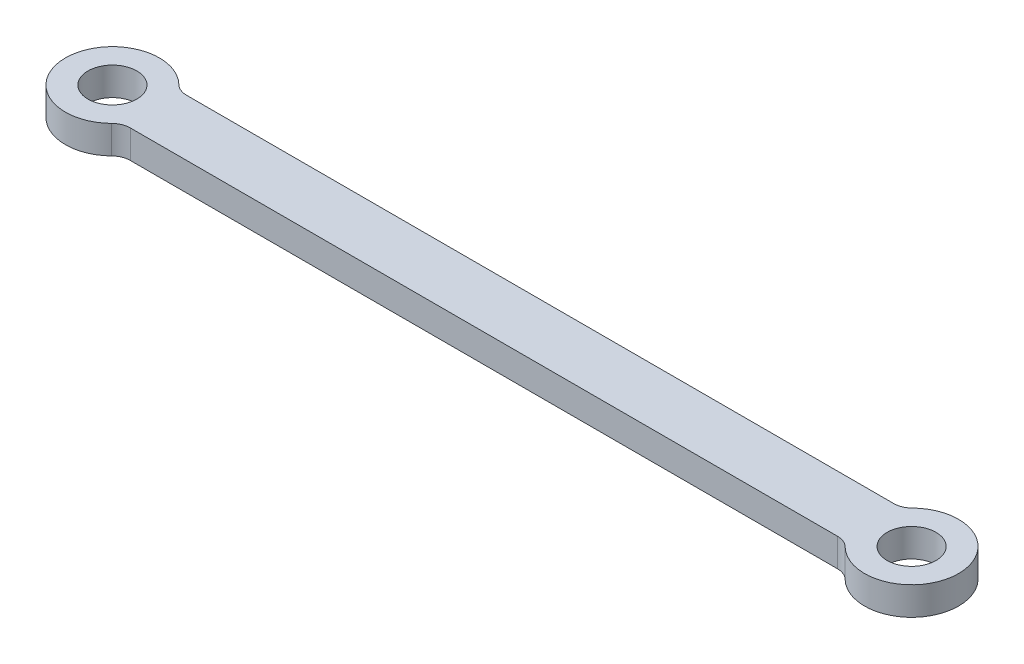
SolidWorks part; units mm, degrees
ref_plane "正面" through (0, 0, 0) normal (0, 0, 1) x (1, 0, 0)
ref_plane "平面" through (0, 0, 0) normal (0, 1, 0) x (1, 0, 0)
ref_plane "右側面" through (0, 0, 0) normal (1, 0, 0) x (0, 0, -1)
sketch "ｽｹｯﾁ1" plane through (0, 0, 0) normal (0, 1, 0) x (1, 0, 0)
  line L0 (-42.5, 0) -> (42.5, 0) construction
  line L1 (-42.5, 3) -> (42.5, 3)
  line L2 (-42.5, -3) -> (42.5, -3)
  arc A0 (-42.5, 3) -> (-42.5, -3) centre (-42.5, 0) ccw
  arc A1 (42.5, -3) -> (42.5, 3) centre (42.5, 0) ccw
  point P2 (0, 0)
  dimension "D2" = 3
  dimension "D3" = 85
extrude "ﾎﾞｽ - 押し出し1" add sketch "ｽｹｯﾁ1" along normal blind 3
sketch "ｽｹｯﾁ2" plane through (0, 3, 0) normal (0, 1, 0) x (1, 0, 0)
  circle A0 centre (-42.5, 0) radius 5
  circle A1 centre (42.5, 0) radius 5
  dimension "D1" = 10
extrude "ﾎﾞｽ - 押し出し2" add sketch "ｽｹｯﾁ2" against normal up to surface (3 mm away) up to face at (0, 0, 0)
sketch "ｽｹｯﾁ3" plane through (0, 3, 0) normal (0, 1, 0) x (1, 0, 0)
  circle A0 centre (-42.5, 0) radius 2.6
  circle A1 centre (42.5, 0) radius 2.6
  dimension "D1" = 5.2
extrude "ｶｯﾄ - 押し出し1" cut sketch "ｽｹｯﾁ3" against normal blind 10
fillet "ﾌｨﾚｯﾄ1" radius 2 4 edges at (38.5, 1.5, 3) (-38.5, 1.5, 3) (38.5, 1.5, -3) (-38.5, 1.5, -3)
